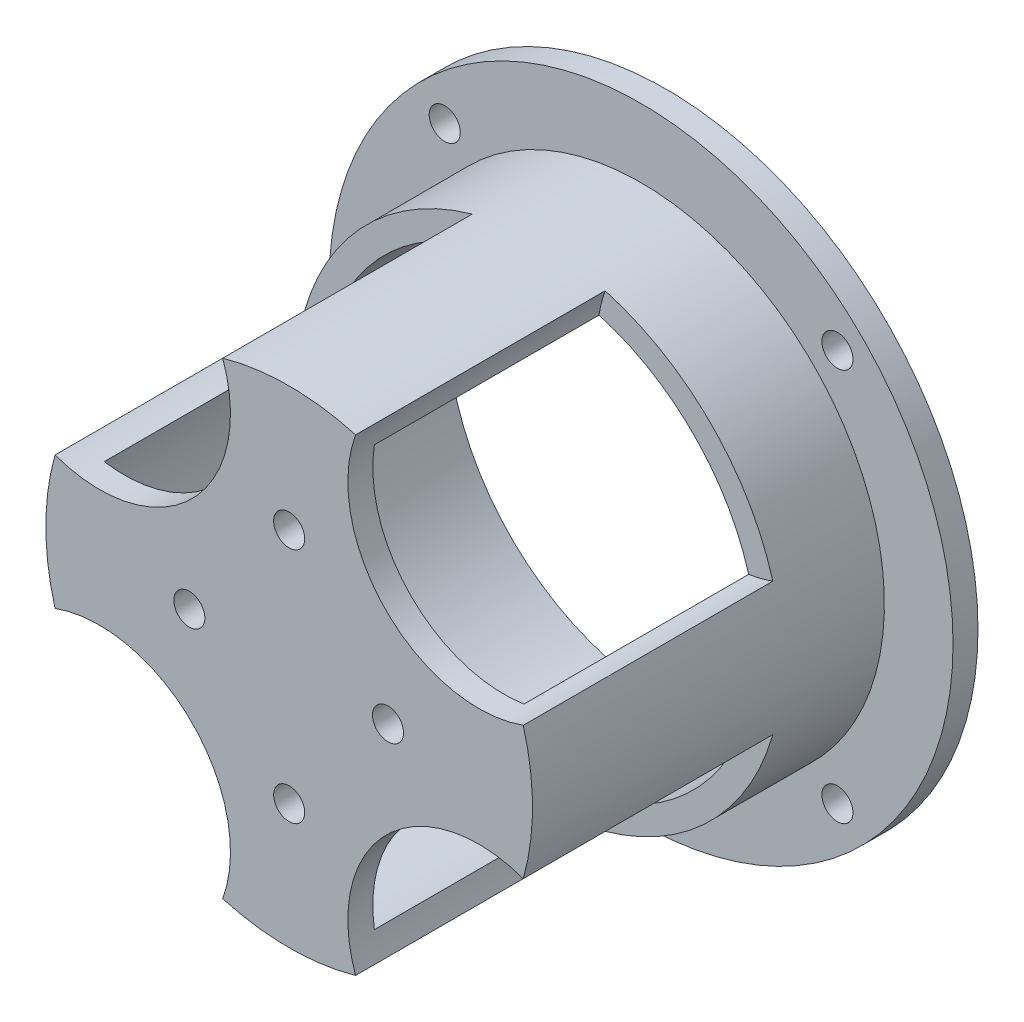
SolidWorks part; units mm, degrees
ref_plane "Спереди" through (0, 0, 0) normal (0, 0, 1) x (1, 0, 0)
ref_plane "Сверху" through (0, 0, 0) normal (0, 1, 0) x (1, 0, 0)
ref_plane "Справа" through (0, 0, 0) normal (1, 0, 0) x (0, 0, -1)
sketch "Эскиз1" plane through (0, 0, 0) normal (0, 1, 0) x (1, 0, 0)
  line L0 (0, 0) -> (0, 14.1) construction
  line L1 (8.75, 1) -> (0, 1)
  line L2 (0, 1) -> (0, 0)
  line L3 (9.75, 15.1) -> (9.75, 0)
  line L5 (8.75, 1) -> (8.75, 15.1)
  line L6 (8.75, 15.1) -> (9.75, 15.1)
  line L7 (0, 0) -> (9.75, 0)
  dimension "D1" = 1
  dimension "D2" = 15.1
  dimension "D3" = 17.5
  dimension "D4" = 1
revolve "Повернуть1" add sketch "Эскиз1" angle 360 about L0
sketch "Эскиз3" plane through (0, 0, 0) normal (0, 0, 1) x (1, 0, 0)
  line L0 (0, 0) -> (7.6014, -7.6014) construction
  line L1 (0, 0) -> (10.75, 0) construction
  circle A0 centre (0, 0) radius 4 construction
  circle A1 centre (0, 0) radius 4.75 construction
  circle A2 centre (-4, 0) radius 0.6225
  circle A3 centre (0, -4.75) radius 0.6225
  circle A4 centre (3.9616, 0) radius 0.6225
  circle A5 centre (0, 4.75) radius 0.6225
  circle A6 centre (0, 0) radius 10.75 construction
  circle A7 centre (7.6014, -7.6014) radius 5.25
  circle A8 centre (-7.6014, -7.6014) radius 5.25
  circle A9 centre (-7.6014, 7.6014) radius 5.25
  circle A10 centre (7.6014, 7.6014) radius 5.25
  point P14 (4.75, 0)
  point P16 (4.75, 0)
  point P17 (4.75, 0)
  point P25 (0, 0)
  point P26 (3.9616, 0)
  point P27 (-4.75, 0)
  point P28 (-4.75, 0)
  point P29 (-4, 0)
  point P30 (0, -4)
  point P31 (0, -4.75)
  point P32 (0, 4)
  point P33 (0, 4.75)
  dimension "D1" = 9.5
  dimension "D2" = 8
  dimension "D3" = 1.245
  dimension "D4" = 1.245
  dimension "D5" = 1.245
  dimension "D6" = 1.245
  dimension "D7" = 21.5
  dimension "D8" = 10.5
  dimension "D9" = 45
  dimension "D10" = 4
extrude "Вырез-Вытянуть1" cut sketch "Эскиз3" against normal blind 10
sketch "Эскиз4" plane through (0, 0, -15.1) normal (0, 0, -1) x (-1, 0, 0)
  circle A0 centre (0, 0) radius 12.5
  circle A1 centre (0, 0) radius 8.75 construction
  circle A2 centre (0, 0) radius 8.75
  dimension "D1" = 25
extrude "Бобышка-Вытянуть1" add sketch "Эскиз4" against normal blind 1
sketch "Эскиз9" plane through (0, 0, -14.1) normal (0, 0, 1) x (1, 0, 0)
  line L0 (0, 0) -> (7.4264, 7.4264) construction
  circle A0 centre (0, 0) radius 11.125 construction
  circle A1 centre (7.8666, 7.8666) radius 0.6225
  circle A2 centre (7.8666, -7.8666) radius 0.6225
  circle A3 centre (-7.8666, -7.8666) radius 0.6225
  circle A4 centre (-7.8666, 7.8666) radius 0.6225
  point P15 (0, 0)
  dimension "D1" = 22.25
  dimension "D2" = 1.245
  dimension "D3" = 4
extrude "Вырез-Вытянуть2" cut sketch "Эскиз9" against normal through all
